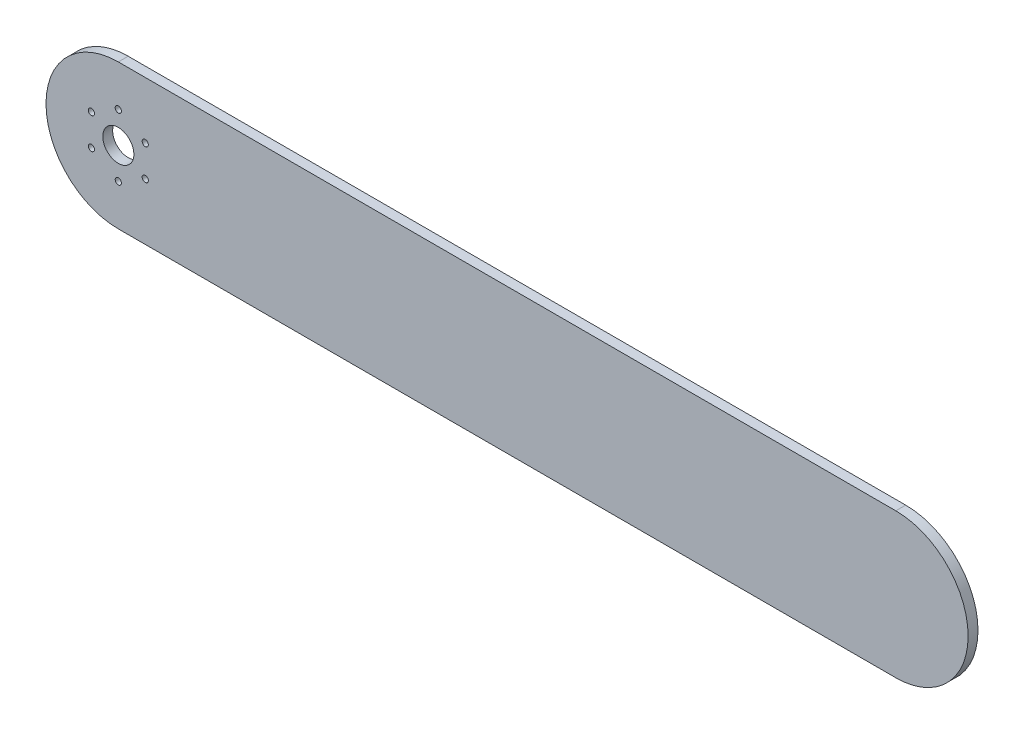
SolidWorks part; units mm, degrees
ref_plane "Front Plane" through (0, 0, 0) normal (0, 0, 1) x (1, 0, 0)
ref_plane "Top Plane" through (0, 0, 0) normal (0, 1, 0) x (1, 0, 0)
ref_plane "Right Plane" through (0, 0, 0) normal (1, 0, 0) x (0, 0, -1)
sketch "Sketch2" plane through (0, 0, 0) normal (0, 0, 1) x (1, 0, 0)
  line L0 (0, 0) -> (500, 0) construction
  line L1 (0, 46.5) -> (500, 46.5)
  line L2 (0, -46.5) -> (500, -46.5)
  arc A0 (0, 46.5) -> (0, -46.5) centre (0, 0) ccw
  arc A1 (500, -46.5) -> (500, 46.5) centre (500, 0) ccw
  circle A2 centre (500, 0) radius 37.25 construction
  circle A3 centre (0, 0) radius 10
  circle A4 centre (0, 20) radius 2
  circle A5 centre (0, 0) radius 20 construction
  circle A6 centre (17.3205, 10) radius 2
  circle A7 centre (17.3205, -10) radius 2
  circle A8 centre (0, -20) radius 2
  circle A9 centre (-17.3205, -10) radius 2
  circle A10 centre (-17.3205, 10) radius 2
  point P3 (250, 0)
  point P27 (0, 0)
  dimension "D2" = 74.5
  dimension "D4" = 20
  dimension "D5" = 4
  dimension "D6" = 40
  dimension "D3" = 46.5
  dimension "D1" = 500
  dimension "D7" = 6
extrude "Boss-Extrude1" add sketch "Sketch2" along normal blind 6.35
equation "\"L1L\"=500"
equation "\"L1Thick\"=6.35"
equation "\"D1@Sketch2\"=\"L1L\""
equation "\"Harm-Drive-Outer\"=74.5"
equation "\"D2@Sketch2\"=\"Harm-Drive-Outer\""
equation "\"D1@Boss-Extrude1\"=\"L1Thick\""
